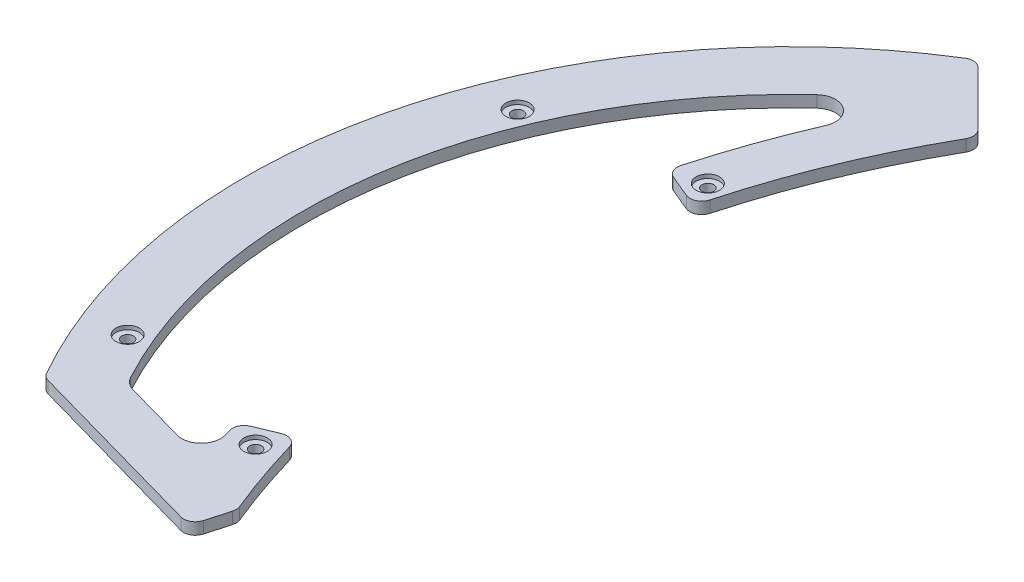
SolidWorks part; units mm, degrees
material "1060 Alloy"
ref_plane "Front Plane" through (0, 0, 0) normal (0, 0, 1) x (1, 0, 0)
ref_plane "Top Plane" through (0, 0, 0) normal (0, 1, 0) x (1, 0, 0)
ref_plane "Right Plane" through (0, 0, 0) normal (1, 0, 0) x (0, 0, -1)
sketch "Sketch1" plane through (0, 0, 0) normal (0, 1, 0) x (1, 0, 0)
  circle A0 centre (0, 0) radius 140
  dimension "D1" = 280
extrude "Boss-Extrude1" add sketch "Sketch1" along normal blind 3
sketch "Sketch17" plane through (0, 0, 0) normal (0, -1, 0) x (1, 0, 0)
  line L0 (-50, 90) -> (-121.2436, 70)
  line L1 (-50, 90) -> (50, 90)
  line L2 (-121.2436, 70) -> (-121.2436, 140)
  line L3 (-121.2436, 140) -> (121.2436, 140)
  line L4 (121.2436, 140) -> (121.2436, 70)
  line L5 (121.2436, 70) -> (50, 90)
  circle A0 centre (0, 0) radius 140 construction
  dimension "D1" = 90
  dimension "D2" = 50
  dimension "D3" = 50
  dimension "D4" = 70
extrude "Cut-Extrude1" cut sketch "Sketch17" against normal up to next
sketch "Sketch19" plane through (0, 3, 0) normal (0, 1, 0) x (1, 0, 0)
  line L0 (-68.5894, 68.5894) -> (68.5894, -68.5894) construction
  line L1 (97, 40.1787) -> (40.1787, 97) construction
  line L2 (40.1787, 97) -> (-40.1787, 97) construction
  line L3 (-40.1787, 97) -> (-97, 40.1787) construction
  line L4 (-97, 40.1787) -> (-97, -40.1787) construction
  line L5 (-97, -40.1787) -> (-40.1787, -97) construction
  line L6 (-40.1787, -97) -> (40.1787, -97) construction
  line L7 (40.1787, -97) -> (97, -40.1787) construction
  line L8 (97, -40.1787) -> (97, 40.1787) construction
  line L9 (68.5894, 68.5894) -> (-68.5894, -68.5894) construction
  circle A0 centre (-79.196, -57.9828) radius 1.5
  circle A1 centre (-79.196, 57.9828) radius 1.5
  circle A2 centre (79.196, 57.9828) radius 1.5
  circle A3 centre (79.196, -57.9828) radius 1.5
  circle A4 centre (0, 0) radius 97 construction
  circle A5 centre (-57.9828, 79.196) radius 1.5
  circle A6 centre (57.9828, 79.196) radius 1.5
  circle A7 centre (57.9828, -79.196) radius 1.5
  circle A8 centre (-57.9828, -79.196) radius 1.5
  dimension "D5" = 3
  dimension "D1" = 15
  dimension "D6" = 97
extrude "Cut-Extrude3" cut sketch "Sketch19" against normal up to next
sketch "Sketch25" plane through (0, 3, 0) normal (0, 1, 0) x (1, 0, 0)
  circle A0 centre (-120, 50) radius 1.5
  circle A1 centre (-120, -50) radius 1.5
  dimension "D1" = 3
  dimension "D2" = 50
  dimension "D3" = 50
  dimension "D4" = 120
extrude "Cut-Extrude10" cut sketch "Sketch25" against normal up to next
sketch "Sketch20" plane through (0, 3, 0) normal (0, 1, 0) x (1, 0, 0)
  line L0 (-72, 120.0666) -> (-50, 98.0666)
  line L1 (-50, 98.0666) -> (50, 98.0666)
  line L2 (50, 98.0666) -> (72, 120.0666)
  arc A1 (121.2436, -70) -> (-121.2436, -70) centre (0, 0) ccw construction
  dimension "D1" = 144
  dimension "D2" = 100
  dimension "D3" = 50
extrude "Cut-Extrude4" cut sketch "Sketch20" against normal up to next
fillet "Fillet2" radius 10 2 edges at (50, 1.5, -98.0666) (-50, 1.5, -98.0666)
sketch "Sketch23" plane through (0, 3, 0) normal (0, 1, 0) x (1, 0, 0)
  line L0 (-67.1106, -74.7122) -> (-73.1897, -96.3671)
  line L1 (-72, 120.0666) -> (-52.9289, 100.9956) construction
  line L2 (-121.2436, -70) -> (-50, -90) construction
  arc A0 (-54.9334, 103) -> (-67.1106, -74.7122) centre (117.6332, 1.902) ccw
  arc A3 (-67.1106, -74.7122) -> (-54.9334, -99.196) centre (117.6332, 1.902) ccw construction
  circle A4 centre (-57.9828, -79.196) radius 1.5 construction
  dimension "D1" = 103
  dimension "D2" = 20
  dimension "D3" = 200
  dimension "D4" = 90
  dimension "D5" = 10
extrude "Cut-Extrude8" cut sketch "Sketch23" against normal through all and the other way through all
sketch "Sketch24" plane through (0, 3, 0) normal (0, 1, 0) x (1, 0, 0)
  line L0 (-87.3571, 55.9666) -> (-76.1692, 51.3049)
  line L1 (-109.1428, -60.9331) -> (-82.3519, -68.4541)
  line L3 (-121.2436, -70) -> (-69.8389, -84.4307) construction
  line L4 (-86.4256, -55.5785) -> (-75.2633, -50.9275)
  line L5 (-120, 50) -> (0, 0) construction
  line L6 (0, 0) -> (-120, -50) construction
  line L7 (-76.1692, 51.3049) -> (-75.2633, -50.9275)
  arc A1 (-87.3571, 55.9666) -> (-67.4898, 105.2147) centre (117.6332, 1.902) cw
  arc A2 (-54.9334, 103) -> (-67.1106, -74.7122) centre (117.6332, 1.902) ccw construction
  arc A3 (-67.4898, 105.2147) -> (-109.1428, -60.9331) centre (0, 0) ccw
  circle A4 centre (-120, 50) radius 5 construction
  circle A5 centre (-120, -50) radius 5 construction
  arc A6 (-82.3519, -68.4541) -> (-86.4256, -55.5785) centre (117.6332, 1.902) cw
  circle A8 centre (-79.196, -57.9828) radius 1.5 construction
  circle A9 centre (-79.196, 57.9828) radius 1.5 construction
  dimension "D2" = 10
  dimension "D3" = 5
  dimension "D4" = 12
  dimension "D5" = 12
  dimension "D1" = 5
  dimension "D6" = 12
extrude "Cut-Extrude9" cut sketch "Sketch24" against normal up to next
fillet "Fillet4" radius 5 3 edges at (-82.3519, 1.5, 68.4541) (-109.1428, 1.5, 60.9331) (-67.4898, 1.5, -105.2147)
fillet "Fillet5" radius 3 9 edges at (-72, 1.5, -120.0666) (-67.1106, 1.5, 74.7122) (-69.8389, 1.5, 84.4307) (-121.2436, 1.5, 70) (-54.9334, 1.5, -103) (-86.4256, 1.5, 55.5785) (-75.2633, 1.5, 50.9275) (-87.3571, 1.5, -55.9666) (-76.1692, 1.5, -51.3049)
sketch "Sketch26" plane through (0, 3, 0) normal (0, -1, 0) x (1, 0, 0)
  circle A0 centre (-79.196, 57.9828) radius 3
  circle A1 centre (-120, 50) radius 3
  circle A2 centre (-120, -50) radius 3
  circle A3 centre (-79.196, -57.9828) radius 3
  dimension "D1" = 6
extrude "Cut-Extrude11" cut sketch "Sketch26" along normal blind 1
equation "\"D3@Sketch20\" = \"D2@Sketch20\" / 2"
